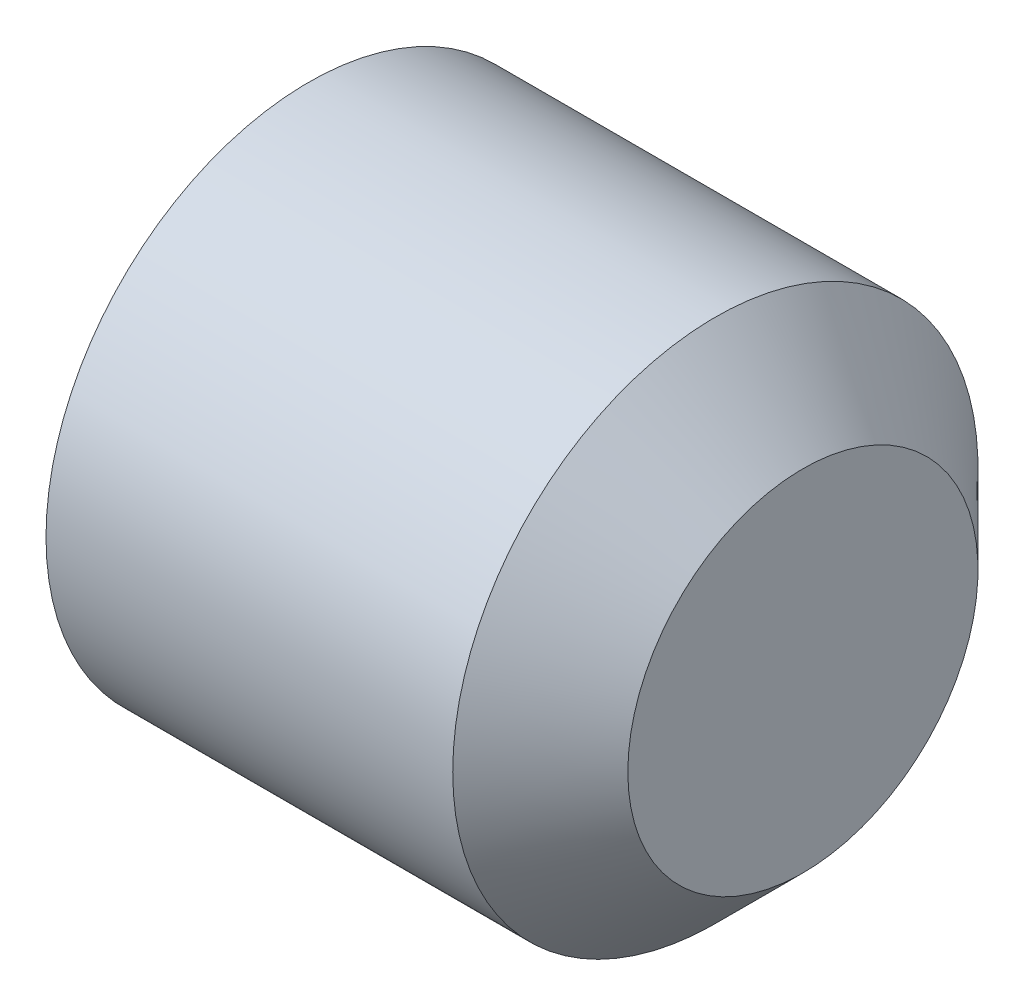
SolidWorks part; units mm, degrees
ref_plane "Front Plane" through (0, 0, 0) normal (0, 0, 1) x (1, 0, 0)
ref_plane "Top Plane" through (0, 0, 0) normal (0, 1, 0) x (1, 0, 0)
ref_plane "Right Plane" through (0, 0, 0) normal (1, 0, 0) x (0, 0, -1)
sketch "Sketch1" plane through (0, 0, 0) normal (0, 0, 1) x (1, 0, 0)
  line L0 (3, 0) -> (3, -1)
  line L1 (3, -1) -> (2.5, -1.5)
  line L2 (2.5, -1.5) -> (0.177, -1.5)
  line L3 (0.177, -1.5) -> (0, -1.1935)
  line L4 (0, -1.1935) -> (0, -0.866)
  line L5 (0, -0.866) -> (0.5, 0)
  line L6 (0.5, 0) -> (3, 0)
  line L7 (0.5, 0) -> (3, 0) construction
revolve "Revolve1" add sketch "Sketch1" angle 360 about L7
cosmetic thread "Cosmetic Thread1" parameters "D1"=3, "D2"=2.387
sketch "Sketch2" plane through (0, 0, 0) normal (1, 0, 0) x (0, 0, -1)
  line L0 (-0.866, 0) -> (-0.433, -0.75)
  line L1 (-0.433, -0.75) -> (0.433, -0.75)
  line L2 (0.433, -0.75) -> (0.866, 0)
  line L3 (0.866, 0) -> (0.433, 0.75)
  line L4 (0.433, 0.75) -> (-0.433, 0.75)
  line L5 (-0.433, 0.75) -> (-0.866, 0)
extrude "Cut-Extrude1" cut sketch "Sketch2" along normal blind 1.2
ref_plane "Plane1" through (3, 0, 0) normal (1, 0, 0) x (0, 0, -1)
ref_plane "IP1 XY" through (0, 0, 0) normal (1, 0, 0) x (0, 0, -1)
ref_plane "IP1 XZ" through (0, 0, 0) normal (0, -1, 0) x (-1, 0, 0)
ref_plane "IP1 YZ" through (0, 0, 0) normal (0, 0, -1) x (-1, 0, 0)
ref_axis "IP1 X" through (0, 0, 80.9) along (0, 0, -1)
ref_axis "IP1 Y" through (0, -50, 0) along (0, 1, 0)
ref_axis "IP1 Z" through (80.9, 0, 0) along (-1, 0, 0)
sketch3d "IP1"
  point P0 (0, 0, 0)
ref_plane "IP2 XY" through (3, 0, 0) normal (1, 0, 0) x (0, 0, -1)
ref_plane "IP2 XZ" through (0, 0, 0) normal (0, -1, 0) x (-1, 0, 0)
ref_plane "IP2 YZ" through (0, 0, 0) normal (0, 0, -1) x (-1, 0, 0)
ref_axis "IP2 X" through (3, 0, 80.9) along (0, 0, -1)
ref_axis "IP2 Y" through (3, -50, 0) along (0, 1, 0)
ref_axis "IP2 Z" through (80.9, 0, 0) along (-1, 0, 0)
sketch3d "IP2"
  point P0 (3, 0, 0)
other "Freeze***"
